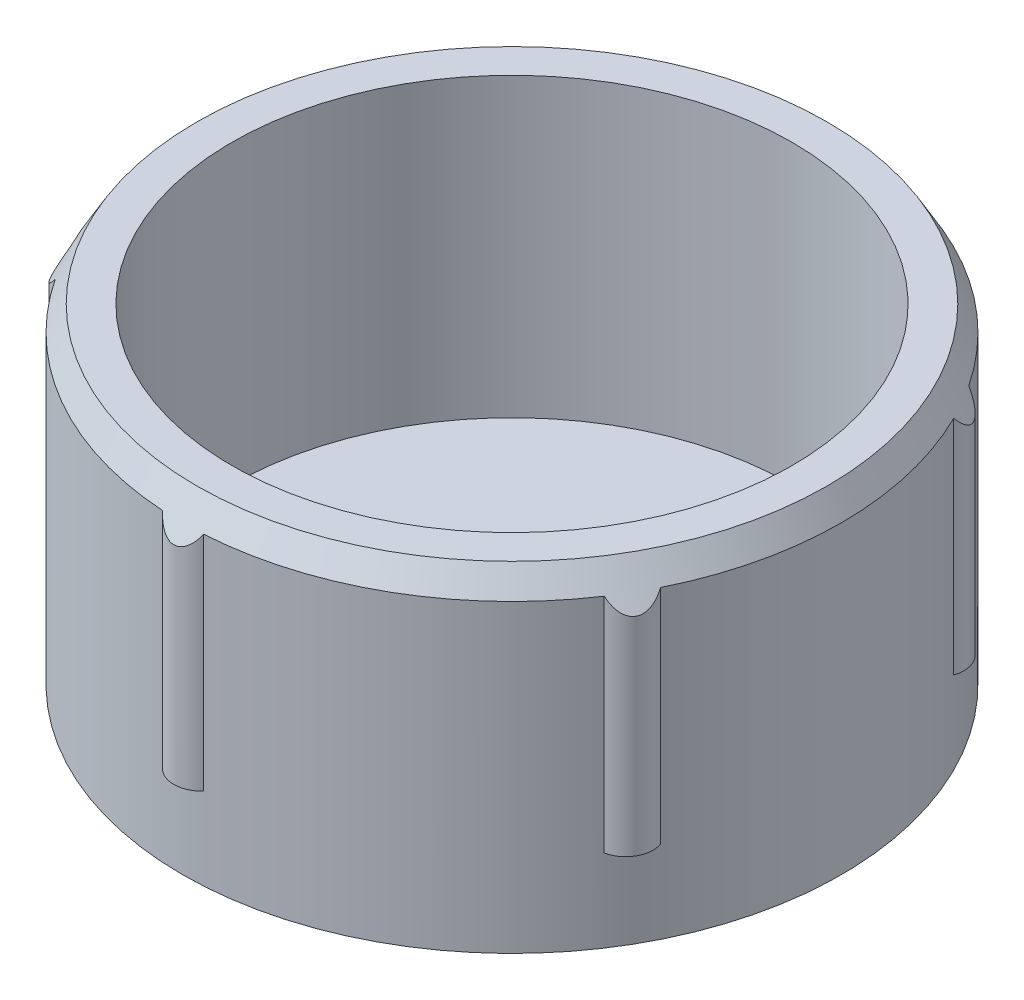
SolidWorks part; units mm, degrees
ref_plane "Front Plane" through (0, 0, 0) normal (0, 0, 1) x (1, 0, 0)
ref_plane "Top Plane" through (0, 0, 0) normal (0, 1, 0) x (1, 0, 0)
ref_plane "Right Plane" through (0, 0, 0) normal (1, 0, 0) x (0, 0, -1)
sketch "Sketch2" plane through (0, 0, 0) normal (0, 0, 1) x (1, 0, 0)
  line L0 (0, 0) -> (-20, 0)
  line L1 (-20, 0) -> (-20, 20)
  line L2 (-20, 20) -> (-17, 20)
  line L3 (-17, 20) -> (-17, 2)
  line L4 (-17, 2) -> (0, 2)
  line L5 (0, 2) -> (0, 0)
  line L6 (0, 0) -> (0, 22119.0408) construction
  dimension "D1" = 40
  dimension "D2" = 3
  dimension "D3" = 20
  dimension "D4" = 2
revolve "Revolve1" add sketch "Sketch2" angle 360 about L6
sketch "Sketch3" plane through (0, 20, 0) normal (0, 1, 0) x (1, 0, 0)
  arc A0 (-1.25, 19.9609) -> (1.25, 19.9609) centre (0, 18.8431) cw
  circle A1 centre (0, 0) radius 20 construction
  arc A2 (-1.25, 19.9609) -> (1.25, 19.9609) centre (0, 0) cw
  arc A3 (16.6616, 11.063) -> (17.9116, 8.8979) centre (0, 0) cw
  arc A4 (16.6616, 11.063) -> (17.9116, 8.8979) centre (16.3186, 9.4216) cw
  arc A5 (17.9116, -8.8979) -> (16.6616, -11.063) centre (0, 0) cw
  arc A6 (17.9116, -8.8979) -> (16.6616, -11.063) centre (16.3186, -9.4216) cw
  arc A7 (1.25, -19.9609) -> (-1.25, -19.9609) centre (0, 0) cw
  arc A8 (1.25, -19.9609) -> (-1.25, -19.9609) centre (0, -18.8431) cw
  arc A9 (-16.6616, -11.063) -> (-17.9116, -8.8979) centre (0, 0) cw
  arc A10 (-16.6616, -11.063) -> (-17.9116, -8.8979) centre (-16.3186, -9.4216) cw
  arc A11 (-17.9116, 8.8979) -> (-16.6616, 11.063) centre (0, 0) cw
  arc A12 (-17.9116, 8.8979) -> (-16.6616, 11.063) centre (-16.3186, 9.4216) cw
  point P24 (0, 0)
  dimension "D1" = 2.5
  dimension "D2" = 20.52
extrude "Boss-Extrude1" add sketch "Sketch3" against normal offset from surface (15 mm away) 5 up to face at (0, 0, -20)
ref_axis "Axis1" through (0, 20, 0) along (0, -1, 0)
sketch "Sketch4" plane through (0, 0, 0) normal (0, 0, 1) x (1, 0, 0)
  line L0 (-21, 16.7679) -> (-18.5566, 21)
  line L1 (-18.5566, 21) -> (-21, 21)
  line L2 (-21, 21) -> (-21, 16.7679)
  point P2 (-20, 20)
  dimension "D1" = 1
  dimension "D2" = 1
  dimension "D3" = 0.75
  dimension "D4" = 30
revolve "Cut-Revolve1" cut sketch "Sketch4" angle 360 about axis through (0, 20, 0) along (0, -1, 0)
sketch "Sketch5" plane through (0, 2, 0) normal (0, 1, 0) x (1, 0, 0)
  circle A0 centre (0, 9.5) radius 1.7
  circle A1 centre (8.2272, -4.75) radius 1.7
  circle A2 centre (-8.2272, -4.75) radius 1.7
  point P10 (0, 0)
  dimension "D3" = 3.4
  dimension "D1" = 9.5
  dimension "D2" = 3
extrude "Cut-Extrude1" cut sketch "Sketch5" against normal up to next
equation "\"D2@Sketch3\"=(1.6in/2)+0.2mm"
